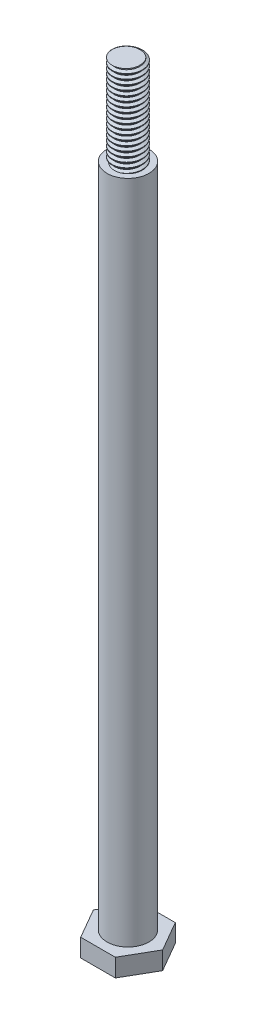
SolidWorks part; units mm, degrees
ref_plane "Front Plane" through (0, 0, 0) normal (0, 0, 1) x (1, 0, 0)
ref_plane "Top Plane" through (0, 0, 0) normal (0, 1, 0) x (1, 0, 0)
ref_plane "Right Plane" through (0, 0, 0) normal (1, 0, 0) x (0, 0, -1)
sketch "Sketch1" plane through (0, 0, 0) normal (0, 1, 0) x (1, 0, 0)
  line L1 (2.8868, 5) -> (-2.8868, 5)
  line L2 (-2.8868, 5) -> (-5.7735, 0)
  line L3 (-5.7735, 0) -> (-2.8868, -5)
  line L4 (-2.8868, -5) -> (2.8868, -5)
  line L5 (2.8868, -5) -> (5.7735, 0)
  line L6 (5.7735, 0) -> (2.8868, 5)
  circle A0 centre (0, 0) radius 5 construction
  dimension "D1" = 10
extrude "Boss-Extrude1" add sketch "Sketch1" along normal blind 3
sketch "Sketch3" plane through (0, 3, 0) normal (0, 1, 0) x (1, 0, 0)
  circle A0 centre (0, 0) radius 3.5
  dimension "D1" = 7
extrude "Boss-Extrude2" add sketch "Sketch3" along normal blind 111
sketch "Sketch4" plane through (0, 114, 0) normal (0, 1, 0) x (1, 0, 0)
  circle A0 centre (0, 0) radius 2.1
  dimension "D1" = 4.2
extrude "Boss-Extrude3" add sketch "Sketch4" along normal blind 15
thread "Thread1" pitch 0.8 method extrude profile "Thread Profile1" start angle 0, offset 1, length 0, pitch 0.8, diameter 4.2
ref_plane "Plane1" through (-2.1, 130, 0) normal (0, 0, 1) x (-1, 0, 0)
sketch "Thread Profile1" plane through (-2.1, 130, 0) normal (0, 0, 1) x (-1, 0, 0)
  line L0 (0, 0) -> (0, 0.8) construction
  line L1 (0, 0) -> (0.433, 0.25)
  line L2 (0.433, 0.25) -> (0.433, 0.35)
  line L3 (0.433, 0.35) -> (0, 0.6)
  line L4 (0.433, 0.3) -> (0, 0.3) construction
  line L11 (0, 0) -> (0, 0.6)
  point P2 (0, 0)
  dimension "Pitch" = 0.8
  dimension "Profile_Angle" = 60
  dimension "Profile_Land" = 0.1
  dimension "Profile_Height" = 0.433
sketch "Sketch8" plane through (0, 129, 0) normal (0, 1, 0) x (1, 0, 0)
  circle A0 centre (0, 0) radius 4.2212
extrude "Cut-Extrude1" cut sketch "Sketch8" along normal blind 8
